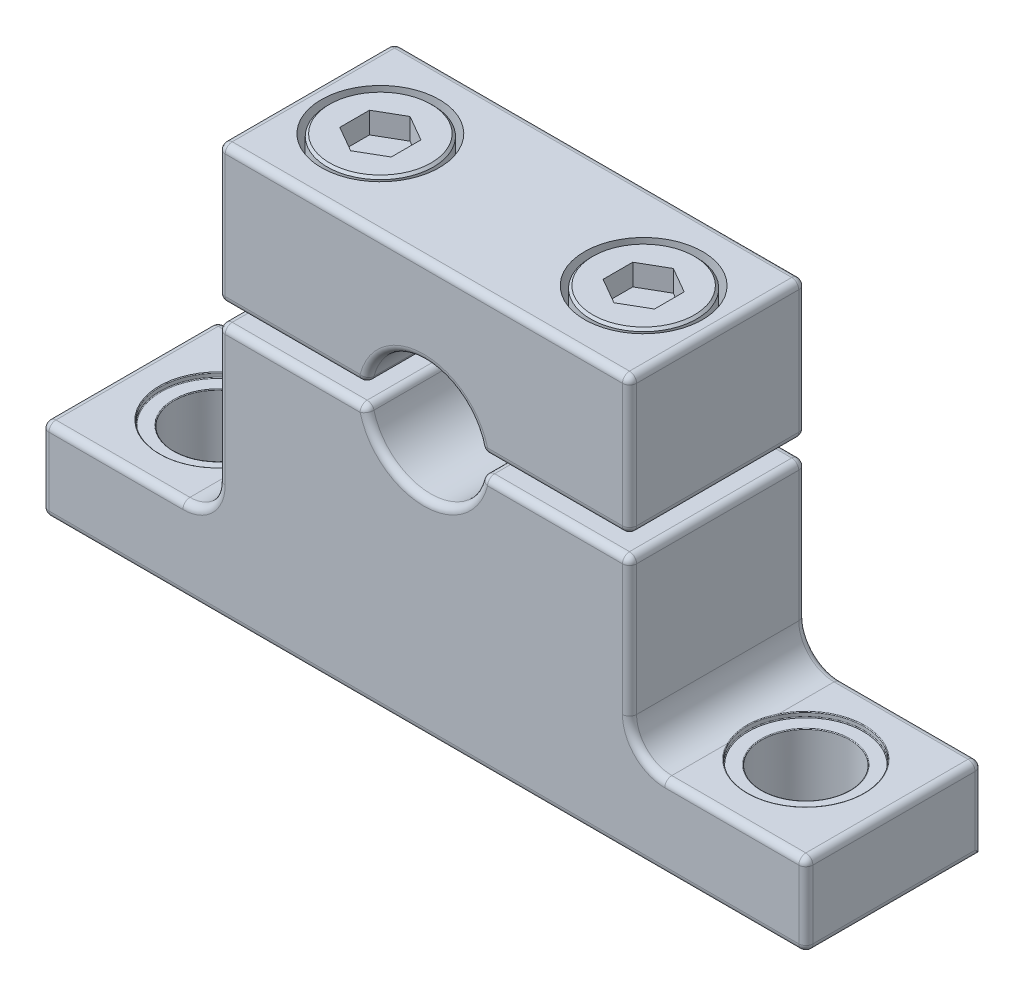
SolidWorks part; units mm, degrees
material "6061 Alloy"
ref_plane "Front" through (0, 0, 0) normal (0, 0, 1) x (1, 0, 0)
ref_plane "Top" through (0, 0, 0) normal (0, 1, 0) x (1, 0, 0)
ref_plane "Right" through (0, 0, 0) normal (1, 0, 0) x (0, 0, -1)
sketch "Sketch1" plane through (0, 0, 0) normal (0, 0, 1) x (1, 0, 0)
  line L0 (0, 22.225) -> (0, 0) construction
  line L1 (-20.6375, 0) -> (20.6375, 0) construction
  line L2 (0, 0) -> (0, 14.2875) construction
  line L3 (-15.875, 0) -> (15.875, 0) construction
  line L4 (14.2875, 0) -> (17.4625, 0) construction
  line L5 (17.4625, 0) -> (17.4625, 1.27) construction
  line L6 (14.2875, 0) -> (14.2875, 1.27) construction
  line L7 (-14.2875, 0) -> (-14.2875, 1.27) construction
  line L8 (-17.4625, 0) -> (-17.4625, 1.27) construction
  line L9 (-14.2875, 0) -> (-17.4625, 0) construction
  line L10 (-11.1125, 14.2875) -> (11.1125, 14.2875) construction
  line L11 (-11.1125, 13.7795) -> (11.1125, 13.7795) construction
  line L12 (-11.1125, 14.7955) -> (11.1125, 14.7955) construction
  line L13 (13.9065, 0) -> (13.9065, 1.27) construction
  line L14 (17.8435, 0) -> (17.8435, 1.27) construction
  line L15 (-13.9065, 0) -> (-13.9065, 1.27) construction
  line L16 (-17.8435, 0) -> (-17.8435, 1.27) construction
  line L17 (-11.0713, 13.7795) -> (11.0713, 13.7795) construction
  line L18 (-11.0713, 14.7955) -> (11.0713, 14.7955) construction
  line L19 (-11.0713, 14.2875) -> (11.0713, 14.2875) construction
  line L20 (-20.6375, 0) -> (-20.6375, 4.445) construction
  line L21 (-20.6375, 4.445) -> (-11.1125, 4.445) construction
  line L22 (-11.1125, 13.7795) -> (-11.1125, 4.445) construction
  line L23 (-11.1125, 14.7955) -> (-11.1125, 22.225) construction
  line L24 (-11.1125, 22.225) -> (11.1125, 22.225) construction
  line L25 (20.6375, 0) -> (20.6375, 4.445) construction
  line L26 (20.6375, 4.445) -> (11.1125, 4.445) construction
  line L27 (11.1125, 13.7795) -> (11.1125, 4.445) construction
  line L28 (11.1125, 14.7955) -> (11.1125, 22.225) construction
  line L29 (0, 22.225) -> (0, 18.7198) construction
  line L30 (0.3175, 18.7198) -> (-0.3175, 18.7198) construction
  line L31 (11.1125, 4.445) -> (11.1125, 0) construction
  circle A0 centre (0, 14.2875) radius 3.175 construction
  arc A1 (-13.0175, 4.445) -> (-11.1125, 6.35) centre (-13.0175, 6.35) ccw construction
  arc A2 (13.0175, 4.445) -> (11.1125, 6.35) centre (13.0175, 6.35) cw construction
  point P5 (0, 0)
  point P9 (0, 14.2875)
  point P11 (0, 0)
  point P12 (15.875, 0)
  point P13 (-15.875, 0)
  point P16 (15.875, 0)
  point P37 (0, 13.7795)
  point P40 (0, 14.7955)
  point P60 (0, 18.7198)
  point P64 (15.875, 4.445)
  dimension "D1" = 1.27
  dimension "D8" = 4.445
  dimension "D12" = 0.635
  dimension "D10" = 1.905
  dimension "D11" = 1.905
  dimension "D9" = 4.7625
  dimension "D13" = 4.7625
  dimension "D3" = 0.508
  dimension "D4" = 0.381
  dimension "D5" = 0.381
  dimension "D6" = 0.381
  dimension "D7" = 0.381
sketch "Sketch3" plane through (0, 0, 0) normal (0, 0, 1) x (1, 0, 0)
  line L0 (-11.1125, 22.225) -> (11.1125, 22.225) construction
  line L1 (11.1125, 14.7955) -> (11.1125, 22.225) construction
  line L2 (-11.1125, 14.7955) -> (11.1125, 14.7955) construction
  line L3 (-11.1125, 14.7955) -> (-11.1125, 22.225) construction
  line L4 (-11.1125, 13.7795) -> (-11.1125, 4.445) construction
  line L5 (-20.6375, 4.445) -> (-11.1125, 4.445) construction
  line L6 (-20.6375, 0) -> (-20.6375, 4.445) construction
  line L7 (-20.6375, 0) -> (20.6375, 0) construction
  line L8 (20.6375, 0) -> (20.6375, 4.445) construction
  line L9 (20.6375, 4.445) -> (11.1125, 4.445) construction
  line L10 (11.1125, 13.7795) -> (11.1125, 4.445) construction
  line L11 (-11.1125, 13.7795) -> (11.1125, 13.7795) construction
  line L12 (-11.1125, 22.225) -> (11.1125, 22.225)
  line L13 (11.1125, 14.7955) -> (11.1125, 22.225)
  line L14 (-11.1125, 14.7955) -> (-3.1341, 14.7955)
  line L15 (-11.1125, 14.7955) -> (-11.1125, 22.225)
  line L16 (-11.1125, 13.7795) -> (-11.1125, 6.35)
  line L17 (-20.6375, 4.445) -> (-13.0175, 4.445)
  line L18 (-20.6375, 0) -> (-20.6375, 4.445)
  line L19 (-20.6375, 0) -> (20.6375, 0)
  line L20 (20.6375, 0) -> (20.6375, 4.445)
  line L21 (20.6375, 4.445) -> (13.0175, 4.445)
  line L22 (11.1125, 13.7795) -> (11.1125, 6.35)
  line L23 (-11.1125, 13.7795) -> (-3.1341, 13.7795)
  line L24 (3.1341, 14.7955) -> (11.1125, 14.7955)
  line L25 (3.1341, 13.7795) -> (11.1125, 13.7795)
  arc A0 (-13.0175, 4.445) -> (-11.1125, 6.35) centre (-13.0175, 6.35) ccw construction
  arc A1 (11.1125, 6.35) -> (13.0175, 4.445) centre (13.0175, 6.35) ccw construction
  circle A2 centre (0, 14.2875) radius 3.175 construction
  arc A3 (-13.0175, 4.445) -> (-11.1125, 6.35) centre (-13.0175, 6.35) ccw
  arc A4 (11.1125, 6.35) -> (13.0175, 4.445) centre (13.0175, 6.35) ccw
  arc A5 (3.1341, 14.7955) -> (-3.1341, 14.7955) centre (0, 14.2875) ccw
  arc A6 (-3.1341, 13.7795) -> (3.1341, 13.7795) centre (0, 14.2875) ccw
extrude "Boss-Extrude1" add sketch "Sketch3" against normal blind 9.525
sketch "Sketch4" plane through (0, 0, 0) normal (0, -1, 0) x (1, 0, 0)
  line L0 (-20.6375, 0) -> (-20.6375, -9.525) construction
  line L1 (-20.6375, 0) -> (-11.1125, 0) construction
  line L2 (-20.6375, -4.7625) -> (20.6375, -4.7625) construction
  line L3 (20.6375, -9.525) -> (20.6375, 0) construction
  line L4 (-15.875, 0) -> (-15.875, -9.525) construction
  line L5 (15.875, 0) -> (15.875, -9.525) construction
  line L6 (-20.6375, -9.525) -> (20.6375, -9.525) construction
  line L7 (0, 0) -> (0, -9.525) construction
  circle A0 centre (-15.875, -4.7625) radius 2.3813
  circle A1 centre (15.875, -4.7625) radius 2.3813
  point P7 (-20.6375, -4.7625)
  dimension "D1" = 4.7625
extrude "Cut-Extrude1" cut sketch "Sketch4" against normal through all
sketch "Sketch6" plane through (0, 4.445, 0) normal (0, 1, 0) x (1, 0, 0)
  line L0 (0, 0) -> (0, 9.525) construction
  line L1 (-20.6375, 0) -> (20.6375, 0) construction
  line L2 (11.1125, 9.525) -> (-11.1125, 9.525) construction
  circle A1 centre (-15.875, 4.7625) radius 2.3813 construction
  circle A2 centre (-15.875, 4.7625) radius 2.3813
  circle A4 centre (-15.875, 4.7625) radius 2.7622
  circle A5 centre (15.875, 4.7625) radius 2.7622
  dimension "D1" = 0.381
sketch "Sketch7" plane through (0, 0, 0) normal (0, 0, 1) x (1, 0, 0)
  line L0 (-20.6375, 4.191) -> (20.6375, 4.191) construction
  line L1 (-11.1125, 13.7795) -> (-11.1125, 0) construction
  line L2 (-20.6375, 0) -> (20.6375, 0) construction
  line L3 (11.1125, 13.7795) -> (11.1125, 0) construction
  line L5 (-20.6375, 0) -> (-20.6375, 4.445) construction
  line L6 (-20.6375, 4.445) -> (-11.1125, 4.445) construction
  line L7 (20.6375, 0) -> (20.6375, 4.445) construction
  line L8 (-15.875, 4.445) -> (-15.875, 4.191) construction
  line L9 (15.875, 4.445) -> (15.875, 4.191) construction
  line L10 (20.6375, 4.445) -> (11.1125, 4.445) construction
  dimension "D1" = 0.254
sketch "Sketch8" plane through (0, 13.7795, 0) normal (0, 1, 0) x (1, 0, 0)
  line L0 (0, 0) -> (0, 9.525) construction
  line L1 (11.1125, 9.525) -> (-11.1125, 9.525) construction
  circle A0 centre (-15.875, 4.7625) radius 2.7622 construction
  circle A1 centre (15.875, 4.7625) radius 2.7622 construction
  circle A2 centre (-15.875, 4.7625) radius 2.7622 construction
  circle A3 centre (15.875, 4.7625) radius 2.7622 construction
  circle A4 centre (-15.875, 4.7625) radius 3.1432
  circle A5 centre (15.875, 4.7625) radius 3.1432
  dimension "D1" = 0.381
extrude "Cut-Extrude3" cut sketch "Sketch8" against normal up to vertex (9.5885 mm away) up to point (-15.875, 4.191, 0)
sketch "Sketch10" plane through (0, 22.225, 0) normal (0, 1, 0) x (1, 0, 0)
  line L0 (-11.1125, 9.525) -> (-11.1125, 0) construction
  line L1 (11.1125, 9.525) -> (11.1125, 0) construction
  line L2 (-11.1125, 9.525) -> (-11.1125, 0) construction
  line L3 (11.1125, 9.525) -> (11.1125, 0) construction
  line L4 (-9.9822, 9.525) -> (-9.9822, 0) construction
  line L5 (0, 0) -> (0, 9.525) construction
  line L6 (9.9822, 9.525) -> (9.9822, 0) construction
  circle A0 centre (-7.112, 4.7625) radius 1.7526 construction
  circle A1 centre (7.112, 4.7625) radius 2.0066
  circle A2 centre (-7.112, 4.7625) radius 2.0066
  circle A3 centre (7.112, 4.7625) radius 1.7526 construction
  circle A4 centre (-7.112, 4.7625) radius 2.8702 construction
  circle A5 centre (7.112, 4.7625) radius 2.8702 construction
extrude "Cut-Extrude4" cut sketch "Sketch10" against normal through all
ref_plane "Plane1" through (0, 0, -4.7625) normal (0, 0, 1) x (1, 0, 0)
sketch "Sketch12" plane through (0, 22.225, 0) normal (0, 1, 0) x (1, 0, 0)
  line L0 (0, 9.525) -> (0, 0) construction
  circle A0 centre (-7.112, 4.7625) radius 3.0607 construction
  circle A1 centre (7.112, 4.7625) radius 3.1877
  circle A2 centre (-7.112, 4.7625) radius 3.1877
  circle A3 centre (7.112, 4.7625) radius 3.0607 construction
  dimension "D2" = 6.3754
  dimension "D1" = 0.127
extrude "Cut-Extrude5" cut sketch "Sketch12" against normal blind 3.8862
sketch "Sketch13" plane through (0, 0, 0) normal (0, 1, 0) x (1, 0, 0)
  line L0 (-7.112, 9.525) -> (-7.112, 0) construction
  line L1 (11.1125, 9.525) -> (-11.1125, 9.525) construction
  line L2 (0, 9.525) -> (0, 0) construction
  line L3 (7.112, 9.525) -> (7.112, 0) construction
  circle A0 centre (-7.112, 4.7625) radius 2.0066 construction
  point P2 (-7.112, 4.7625)
  point P9 (-7.112, 9.525)
  point P10 (-7.112, 0)
  point P17 (7.112, 9.525)
  point P18 (7.112, 0)
  dimension "D1" = 4.0132
sketch "Sketch15" plane through (0, 0, -4.7625) normal (0, 0, 1) x (1, 0, 0)
  line L0 (-7.112, 4.191) -> (-7.112, 22.225) construction
  line L1 (-7.112, 22.225) -> (-9.9822, 22.225) construction
  line L2 (-9.9822, 22.225) -> (-9.9822, 18.7198) construction
  line L3 (-9.9822, 18.7198) -> (-8.8646, 18.7198) construction
  line L4 (-8.8646, 18.7198) -> (-8.8646, 4.191) construction
  line L5 (-8.8646, 4.191) -> (-7.112, 4.191) construction
  line L6 (-20.6375, 4.191) -> (20.6375, 4.191) construction
  line L8 (-11.1125, 22.225) -> (11.1125, 22.225) construction
  line L9 (-7.112, 4.191) -> (-7.112, 22.225)
  line L10 (-7.112, 22.225) -> (-9.9822, 22.225)
  line L11 (-9.9822, 22.225) -> (-9.9822, 18.7198)
  line L12 (-9.9822, 18.7198) -> (-8.8646, 18.7198)
  line L13 (-8.8646, 18.7198) -> (-8.8646, 4.191)
  line L14 (-8.8646, 4.191) -> (-7.112, 4.191)
  dimension "D2" = 2.8702
  dimension "D1" = 3.5052
  dimension "D3" = 1.7526
revolve "Revolve1" add sketch "Sketch15" angle 360 about L9
chamfer "Chamfer1" distance 0.127 angle 45 1 edges at (-4.2418, 22.225, -4.7625)
sketch "Sketch16" plane through (0, 22.225, 0) normal (0, 1, 0) x (1, 0, 0)
  line L0 (-7.112, 9.525) -> (-7.112, 0) construction
  line L1 (-7.112, 6.3665) -> (-8.5011, 5.5645)
  line L2 (-8.5011, 5.5645) -> (-8.5011, 3.9605)
  line L3 (-8.5011, 3.9605) -> (-7.112, 3.1585)
  line L4 (-7.112, 3.1585) -> (-5.7229, 3.9605)
  line L5 (-5.7229, 3.9605) -> (-5.7229, 5.5645)
  line L6 (-5.7229, 5.5645) -> (-7.112, 6.3665)
  circle A0 centre (-7.112, 4.7625) radius 1.3891 construction
  dimension "Hex Size" = 2.7781
extrude "Cut-Extrude6" cut sketch "Sketch16" against normal blind 1.1567
mirror "Mirror1" about plane through (0, 0, 0) normal (1, 0, 0) of bodies 121 119
fillet "Fillet1" radius 0.381 18 edges at (0, 22.225, -9.525) (-11.1125, 22.225, -4.7625) (-11.1125, 18.5102, -9.525) (-11.1125, 18.5102, 0) (11.1125, 18.5103, -9.525) (11.1125, 22.225, -4.7625) (11.1125, 18.5103, 0) (0, 22.225, 0) (11.1125, 14.7955, -4.7625) (7.1233, 14.7955, -9.525) (-7.1233, 14.7955, -9.525) (-11.1125, 14.7955, -4.7625) (-7.1233, 14.7955, 0) (7.1233, 14.7955, 0) (0, 17.4625, -9.525) (0, 17.4625, 0) (3.1341, 14.7955, -4.7625) (-3.1341, 14.7955, -4.7625)
fillet "Fillet2" radius 0.381 31 edges at (16.8275, 4.445, -9.525) (11.6705, 5.003, -9.525) (11.1125, 10.0648, 0) (11.6705, 5.003, 0) (-16.8275, 4.445, 0) (-11.6705, 5.003, 0) (-16.8275, 4.445, -9.525) (-11.6705, 5.003, -9.525) (11.1125, 10.0648, -9.525) (20.6375, 0, -4.7625) (20.6375, 2.2225, -9.525) (20.6375, 4.445, -4.7625) (16.8275, 4.445, 0) (20.6375, 2.2225, 0) (0, 0, 0) (-20.6375, 2.2225, -9.525) (-20.6375, 0, -4.7625) (-20.6375, 4.445, -4.7625) (-20.6375, 2.2225, 0) (-11.1125, 10.0648, 0) (-11.1125, 10.0648, -9.525) (11.1125, 13.7795, -4.7625) (-11.1125, 13.7795, -4.7625) (-7.1233, 13.7795, 0) (7.1233, 13.7795, 0) (7.1233, 13.7795, -9.525) (-7.1233, 13.7795, -9.525) (0, 11.1125, -9.525) (0, 11.1125, 0) (3.1341, 13.7795, -4.7625) (-3.1341, 13.7795, -4.7625)
fillet "Fillet3" radius 0.0381 8 edges at (-19.0182, 4.191, -4.7625) (19.0182, 4.191, -4.7625) (19.0182, 4.445, -4.7625) (12.732, 4.4665, -4.8055) (18.2562, 4.191, -4.7625) (-12.7856, 4.4592, -4.183) (-19.0183, 4.445, -4.7625) (-18.2562, 4.191, -4.7625)
sketch "Sketch17" plane through (0, 0, 0) normal (0, 0, 1) x (1, 0, 0)
  line L0 (0, 0) -> (0, 22.225) construction
  line L1 (-10.7315, 22.225) -> (10.7315, 22.225) construction
  line L2 (-11.1125, 11.1125) -> (11.0409, 11.1125) construction
  line L3 (-11.1125, 6.35) -> (-11.1125, 13.3985) construction
  point P9 (0, 11.1125)
ref_plane "Contact Plane 1" through (-20.6375, 0, 0) normal (-1, 0, 0) x (0, 0, 1)
ref_plane "Contact Plane 2" through (20.6375, 0, 0) normal (1, 0, 0) x (0, 0, -1)
ref_plane "Contact Plane 3" through (0, 0, 0) normal (-1, 0, 0) x (0, 0, 1)
ref_plane "Contact Plane 4" through (0, 0, -4.7625) normal (0, 0, 1) x (1, 0, 0)
ref_plane "Contact Plane 5" through (0, 11.1125, 0) normal (0, 1, 0) x (1, 0, 0)
ref_axis "Center Axis 1" through (0, -0.6699, -4.7625) along (0, 1, 0)
ref_axis "Center Axis 2" through (22.2822, 11.1125, -4.7625) along (-1, 0, 0)
equation "\"D8@Sketch1\"=\"Oall Ht@Sketch1\"*.20"
equation "\"D1@Cut-Extrude5\"=\"HeadDp@Sketch1\"+.015"
equation "\"D1@Sketch15\"=\"HeadDp@Sketch1\""
equation "\"D3@Sketch15\"=\"ThrdDia@Sketch10\"*.5"
equation "\"D1@Cut-Extrude6\"= \"HeadDp@Sketch1\"*.33"
equation "\"D2@Sketch12\"=\"Head Dia@Sketch10\"+.025"
equation "\"D2@Sketch15\"=\"Head Dia@Sketch10\"*.50"
equation "\"D13@Sketch1\"=\"D9@Sketch1\""
